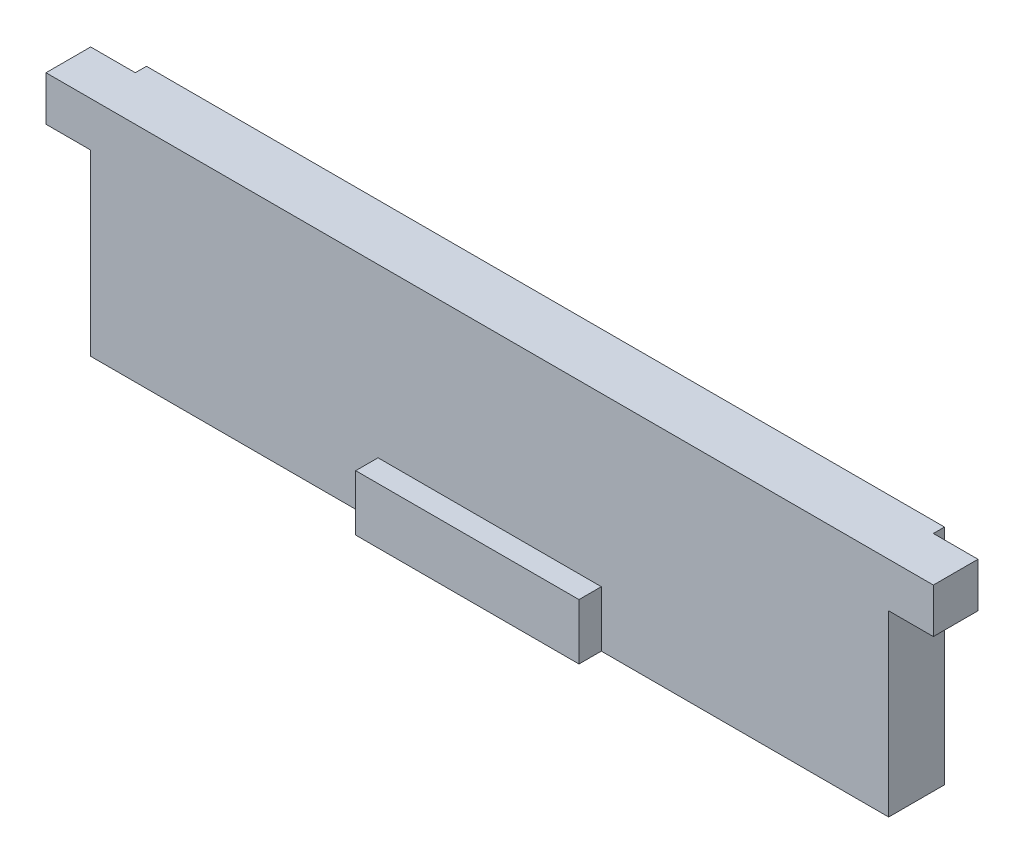
SolidWorks part; units mm, degrees
ref_plane "前视基准面" through (0, 0, 0) normal (0, 0, 1) x (1, 0, 0)
ref_plane "上视基准面" through (0, 0, 0) normal (0, 1, 0) x (1, 0, 0)
ref_plane "右视基准面" through (0, 0, 0) normal (1, 0, 0) x (0, 0, -1)
other "Configuration Table"
sketch "草图1" plane through (0, 0, 0) normal (0, 1, 0) x (1, 0, 0)
  line L5 (0, 0) -> (71.4852, 0)
  line L6 (0, 0) -> (0, 5)
  line L7 (0, 5) -> (71.4852, 5)
  line L8 (71.4852, 0) -> (71.4852, 5)
extrude "凸台-拉伸1" add sketch "草图1" along normal blind 20
sketch "草图3" plane through (0, 0, 0) normal (0, 0, 1) x (1, 0, 0)
  line L0 (0, 0) -> (71.4852, 0) construction
  line L1 (35.7426, 0) -> (45.7426, 0)
  line L2 (35.7426, 0) -> (35.7426, 5)
  line L3 (35.7426, 5) -> (45.7426, 5)
  line L4 (45.7426, 0) -> (45.7426, 5)
  line L6 (35.7426, 0) -> (25.7426, 0)
  line L7 (35.7426, 0) -> (35.7426, 5)
  line L8 (35.7426, 5) -> (25.7426, 5)
  line L9 (25.7426, 0) -> (25.7426, 5)
  line M9 (0, 0) -> (71.4852, 0)
extrude "凸台-拉伸3" add sketch "草图3" along normal blind 2 contours L4 L3 L2 M9 | L9 L2 L8 M9 region at (40.7426, 2.5, 0) region at (30.7426, 2.5, 0)
sketch "草图4" plane through (0, 20, 0) normal (0, 1, 0) x (1, 0, 0)
  line L1 (0, 0) -> (-4, 0)
  line L2 (0, 0) -> (0, 4)
  line L3 (0, 4) -> (-4, 4)
  line L4 (-4, 0) -> (-4, 4)
  line L5 (71.4852, 0) -> (75.4852, 0)
  line L6 (71.4852, 0) -> (71.4852, 4)
  line L7 (71.4852, 4) -> (75.4852, 4)
  line L8 (75.4852, 0) -> (75.4852, 4)
extrude "凸台-拉伸4" add sketch "草图4" against normal blind 4
